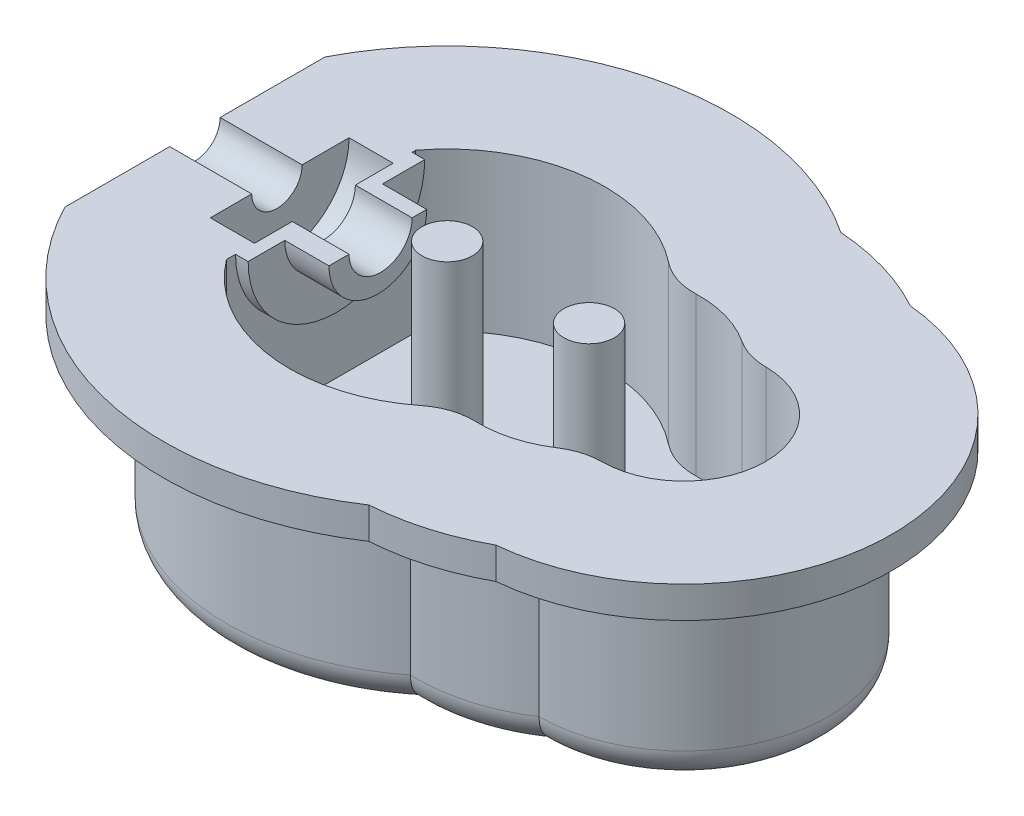
SolidWorks part; units mm, degrees
ref_plane "Front Plane" through (0, 0, 0) normal (0, 0, 1) x (1, 0, 0)
ref_plane "Top Plane" through (0, 0, 0) normal (0, 1, 0) x (1, 0, 0)
ref_plane "Right Plane" through (0, 0, 0) normal (1, 0, 0) x (0, 0, -1)
sketch "Sketch1" plane through (0, 0, 0) normal (0, 1, 0) x (1, 0, 0)
  line L0 (-2125.8372, 0) -> (2252.6955, 0) construction
  line L5 (-57.5, -15) -> (-57.5, 15)
  line L7 (-67.5, -18.0278) -> (-67.5, 18.0278)
  circle A1 centre (0, 0) radius 11
  circle A2 centre (-15, 0) radius 7.5 construction
  circle A3 centre (-37.5, 0) radius 15 construction
  circle A4 centre (0, 0) radius 7.5 construction
  circle A5 centre (-37.5, 0) radius 4
  circle A6 centre (-15, 0) radius 4
  arc A10 (-22.0238, 19.6338) -> (-57.5, 15) centre (-37.5, 0) ccw
  arc A11 (-15.5303, -17.492) -> (-5.4068, -14.6363) centre (-15, 0) ccw
  arc A12 (0.0424, -12.9999) -> (0.0424, 12.9999) centre (0, 0) ccw
  arc A13 (-57.5, -15) -> (-22.0238, -19.6338) centre (-37.5, 0) ccw
  circle A14 centre (-15, 0) radius 17.5 construction
  circle A15 centre (-37.5, 0) radius 25 construction
  circle A16 centre (0, 0) radius 13 construction
  arc A17 (-5.4068, 14.6363) -> (-15.5303, 17.492) centre (-15, 0) ccw
  arc A18 (0.0424, -12.9999) -> (-5.4068, -14.6363) centre (0.075, -22.9999) ccw
  arc A19 (0.0424, 12.9999) -> (-5.4068, 14.6363) centre (0.075, 22.9999) cw
  arc A20 (-15.5303, 17.492) -> (-22.0238, 19.6338) centre (-15.8333, 27.4874) cw
  arc A21 (-15.5303, -17.492) -> (-22.0238, -19.6338) centre (-15.8333, -27.4874) ccw
  arc A31 (0.075, -22.9999) -> (0.075, 22.9999) centre (0, 0) ccw
  arc A32 (0.075, 22.9999) -> (0.075, 22.9999) centre (0.075, 22.9999) cw
  arc A33 (0.075, 22.9999) -> (-15.8333, 27.4874) centre (-15, 0) ccw
  arc A34 (-15.8333, 27.4874) -> (-15.8333, 27.4874) centre (-15.8333, 27.4874) cw
  arc A35 (-15.8333, 27.4874) -> (-67.5, 18.0278) centre (-37.5, 0) ccw
  arc A36 (-67.5, -18.0278) -> (-15.8333, -27.4874) centre (-37.5, 0) ccw
  arc A37 (-15.8333, -27.4874) -> (-15.8333, -27.4874) centre (-15.8333, -27.4874) ccw
  arc A38 (-15.8333, -27.4874) -> (0.075, -22.9999) centre (-15, 0) ccw
  arc A39 (0.075, -22.9999) -> (0.075, -22.9999) centre (0.075, -22.9999) ccw
  point P7 (1088.1233, 0)
  point P9 (919.1687, 0)
  point P19 (991.1425, 0)
  point P22 (1072.1233, 0)
  point P24 (1042.1233, 0)
  point P33 (-2.925, 12.6667)
  point P38 (-9, 0)
  point P58 (0, 0)
  point P59 (0, 0)
  dimension "D1" = 30
  dimension "D2" = 22
  dimension "D4" = 15
  dimension "D5" = 15
  dimension "D6" = 8
  dimension "D3" = 8
  dimension "D7" = 10
  dimension "D8" = 10
  dimension "D11" = 10
  dimension "D9" = 2
  dimension "D10" = 30
  dimension "D12" = 10
extrude "Boss-Extrude1" add sketch "Sketch1" along normal blind 10 contours A21 A11 A18 A12 A19 A17 A20 A10 L5 A13 A5 A1 A6 | A5 | A6 | A1 region at (-31.9057, 0, 0) region at (0, 0, 0) region at (-15, 0, 0) region at (-37.5, 0, 0)
extrude "Boss-Extrude2" add sketch "Sketch1<3>" along normal blind 30 contours A36 A11 A21 A13 L5 A10 A20 A17 A19 A12 A18 region at (-66.3559, 0, 0)
sketch "Sketch1<3>" plane through (0, 0, 0) normal (0, 1, 0) x (1, 0, 0) same geometry as "Sketch1"
sketch "Sketch2" plane through (0, 30, 0) normal (0, 1, 0) x (1, 0, 0)
  line L0 (-57.5, -15) -> (-57.5, 15) construction
  line L1 (-57.5, -15) -> (-57.5, 15)
  line L2 (-77.5, -20.6155) -> (-77.5, 20.6155)
  arc A0 (-57.5, -15) -> (-22.0238, -19.6338) centre (-37.5, 0) ccw construction
  arc A1 (-15.5303, -17.492) -> (-22.0238, -19.6338) centre (-15.8333, -27.4874) ccw construction
  arc A2 (-15.5303, -17.492) -> (-5.4068, -14.6363) centre (-15, 0) ccw construction
  arc A3 (0.0424, -12.9999) -> (-5.4068, -14.6363) centre (0.075, -22.9999) ccw construction
  arc A4 (0.0424, -12.9999) -> (0.0424, 12.9999) centre (0, 0) ccw construction
  arc A5 (-5.4068, 14.6363) -> (0.0424, 12.9999) centre (0.075, 22.9999) ccw construction
  arc A6 (-5.4068, 14.6363) -> (-15.5303, 17.492) centre (-15, 0) ccw construction
  arc A7 (-22.0238, 19.6338) -> (-15.5303, 17.492) centre (-15.8333, 27.4874) ccw construction
  arc A8 (-22.0238, 19.6338) -> (-57.5, 15) centre (-37.5, 0) ccw construction
  arc A9 (-57.5, -15) -> (-22.0238, -19.6338) centre (-37.5, 0) ccw
  arc A10 (-15.5303, -17.492) -> (-22.0238, -19.6338) centre (-15.8333, -27.4874) ccw
  arc A11 (-15.5303, -17.492) -> (-5.4068, -14.6363) centre (-15, 0) ccw
  arc A12 (0.0424, -12.9999) -> (-5.4068, -14.6363) centre (0.075, -22.9999) ccw
  arc A13 (0.0424, -12.9999) -> (0.0424, 12.9999) centre (0, 0) ccw
  arc A14 (-5.4068, 14.6363) -> (0.0424, 12.9999) centre (0.075, 22.9999) ccw
  arc A15 (-5.4068, 14.6363) -> (-15.5303, 17.492) centre (-15, 0) ccw
  arc A16 (-22.0238, 19.6338) -> (-15.5303, 17.492) centre (-15.8333, 27.4874) ccw
  arc A17 (-22.0238, 19.6338) -> (-57.5, 15) centre (-37.5, 0) ccw
  arc A18 (-77.5, -20.6155) -> (-12.5, -37.4166) centre (-37.5, 0) ccw
  arc A19 (-12.5, -37.4166) -> (-12.5, -37.4166) centre (-12.5, -37.4166) ccw
  arc A20 (-12.5, -37.4166) -> (3.075, -32.8564) centre (-15, 0) ccw
  arc A21 (3.075, -32.8564) -> (3.075, -32.8564) centre (3.075, -32.8564) ccw
  arc A22 (3.075, -32.8564) -> (3.075, 32.8564) centre (0, 0) ccw
  arc A23 (3.075, 32.8564) -> (3.075, 32.8564) centre (3.075, 32.8564) ccw
  arc A24 (3.075, 32.8564) -> (-12.5, 37.4166) centre (-15, 0) ccw
  arc A25 (-12.5, 37.4166) -> (-12.5, 37.4166) centre (-12.5, 37.4166) ccw
  arc A26 (-12.5, 37.4166) -> (-77.5, 20.6155) centre (-37.5, 0) ccw
  dimension "D1" = 20
extrude "Boss-Extrude3" add sketch "Sketch2" along normal blind 5
sketch "Sketch3" plane through (-77.5, 0, 0) normal (-1, 0, 0) x (0, 0, 1)
  line L0 (-20.6155, 35) -> (20.6155, 35) construction
  circle A0 centre (0, 35) radius 4
  dimension "D1" = 8
sketch "Sketch4" plane through (0, 35, 0) normal (0, 1, 0) x (1, 0, 0)
  line L0 (-77.5, 0) -> (43.4244, 0.8746) construction
  line L1 (-77.5, 4) -> (-77.5, -4) construction
sketch "Sketch5" plane through (0, 0, 0) normal (0, 0, 1) x (1, 0, 0)
  line L0 (-50, 0) -> (-50, 51) construction
  line L1 (-77.5, 35) -> (43.4244, 35) construction
  line L3 (-67.5, 0) -> (-15.8333, 0) construction
  point P2 (-50, 35)
  point P3 (0, 0)
  point P7 (-50, 0)
  point P10 (0, 0)
  dimension "D1" = 50
  dimension "D2" = 51
sketch "Sketch6" plane through (-57.5, 0, 0) normal (1, 0, 0) x (0, 0, -1)
  line L0 (0, 35) -> (0.8746, 35) construction
  circle A0 centre (0.4373, 35) radius 11
  dimension "D1" = 22
extrude "Cut-Extrude2" cut sketch "Sketch6" against normal blind 7
extrude "Cut-Extrude3" cut sketch "Sketch3" against normal up to next
fillet "Fillet1" radius 5 6 edges at (-43.8033, 0, 34.4277) (-67.5, 0, 0) (-7.534, 0, -26.4671) (-43.8033, 0, -34.4277) (23, 0, 0) (-7.534, 0, 26.4671)
extrude "Boss-Extrude4" add sketch "Sketch1<4>" along normal blind 30 from offset 10 separate body contours A1 A6 | A5 region at (-15, 0, 0) region at (-37.5, 0, 0)
sketch "Sketch1<4>" plane through (0, 0, 0) normal (0, 1, 0) x (1, 0, 0) same geometry as "Sketch1"
sketch "Sketch7" plane through (0, 10, 0) normal (0, -1, 0) x (1, 0, 0)
  circle A0 centre (0, 0) radius 11
  point P3 (0, 0)
extrude "Cut-Extrude5" cut sketch "Sketch7" along normal up to next (10 mm away) from offset 3
sketch "Sketch8" plane through (0, 7, 0) normal (0, -1, 0) x (1, 0, 0)
  circle A0 centre (0, 0) radius 4
  dimension "D1" = 8
extrude "Cut-Extrude6" cut sketch "Sketch8" against normal through all
sketch "Sketch9" plane through (-57.5, 0, 0) normal (1, 0, 0) x (0, 0, -1)
  line L2 (-13.5627, 35) -> (-10.5627, 35)
  line L3 (11.4373, 35) -> (14.4373, 35)
  line L4 (-4.5627, 35) -> (-10.5627, 35)
  line L5 (11.4373, 35) -> (5.4373, 35)
  arc A0 (-10.5627, 35) -> (11.4373, 35) centre (0.4373, 35) ccw construction
  arc A1 (-10.5627, 35) -> (11.4373, 35) centre (0.4373, 35) ccw
  arc A2 (-13.5627, 35) -> (14.4373, 35) centre (0.4373, 35) ccw
  arc A3 (-4.5627, 35) -> (5.4373, 35) centre (0.4373, 35) ccw
  line M1 (15, 35) -> (11.4373, 35)
  arc M2 (11.4373, 35) -> (-10.5627, 35) centre (0.4373, 35) cw
  line M3 (-10.5627, 35) -> (-15, 35)
  dimension "D1" = 3
  dimension "D2" = 6
extrude "Boss-Extrude8" add sketch "Sketch9" along normal blind 9 contours A3 L4 L5 M2 | A2 M3 M1 M2 region at (-57.5, 34.687, 12.0627) region at (-57.5, 29.6683, -0.4373)
sketch "Sketch11" plane through (-48.5, 0, 0) normal (1, 0, 0) x (0, 0, -1)
  line L0 (14.4373, 35) -> (5.4373, 35) construction
  line L1 (-4.5627, 35) -> (-13.5627, 35) construction
  line L2 (-13.5627, 35) -> (-7.75, 35)
  line L3 (7.75, 35) -> (14.4373, 35)
  arc A0 (7.75, 35) -> (-7.75, 35) centre (0, 35) cw
  arc A1 (-13.5627, 35) -> (14.4373, 35) centre (0.4373, 35) ccw construction
  arc A2 (-13.5627, 35) -> (14.4373, 35) centre (0.4373, 35) ccw
  dimension "D1" = 7.75
extrude "Cut-Extrude7" cut sketch "Sketch11" against normal blind 7
